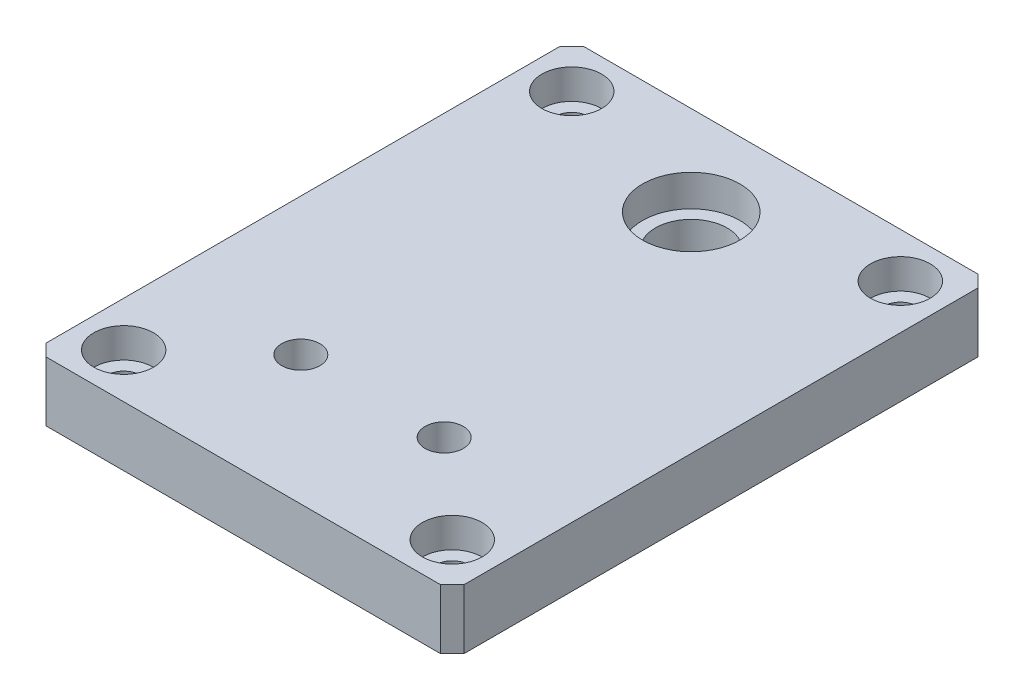
SolidWorks part; units mm, degrees
ref_plane "Front Plane" through (0, 0, 0) normal (0, 0, 1) x (1, 0, 0)
ref_plane "Top Plane" through (0, 0, 0) normal (0, 1, 0) x (1, 0, 0)
ref_plane "Right Plane" through (0, 0, 0) normal (1, 0, 0) x (0, 0, -1)
sketch "Sketch1" plane through (0, 0, 0) normal (0, 1, 0) x (1, 0, 0)
  line L1 (-35, -45) -> (35, -45)
  line L2 (-35, -45) -> (-35, 45)
  line L3 (-35, 45) -> (35, 45)
  line L4 (35, -45) -> (35, 45)
  line L5 (-35, -45) -> (35, 45) construction
  line L6 (-35, 45) -> (35, -45) construction
  point P0 (0, 0)
  dimension "D1" = 70
  dimension "D2" = 90
extrude "Boss-Extrude1" add sketch "Sketch1" along normal blind 10
sketch "Sketch4" plane through (0, 10, 0) normal (0, 1, 0) x (1, 0, 0)
  line L0 (-35, 45) -> (-35, -45) construction
  line L1 (35, 45) -> (-35, 45) construction
  line L3 (35, -45) -> (35, 45) construction
  line L4 (-35, -45) -> (35, -45) construction
  point P0 (-27.5, -37.5)
  point P2 (-27.5, 37.5)
  point P4 (27.5, 37.5)
  point P6 (27.5, -37.5)
  dimension "D1" = 7.5
  dimension "D2" = 7.5
  dimension "D3" = 7.5
  dimension "D4" = 7.5
hole_wizard "CBORE for M5 SHCS1" positions "Sketch4" profile "Sketch3" counterbore size "M5" standard "ANSI Metric" end condition through all
sketch "Sketch3" plane through (-27.5, 10, 37.5) normal (1, 0, 0) x (0, 0, 1)
  line L0 (0, 0) -> (0, 10)
  line L1 (0, 10) -> (2.75, 10)
  line L3 (2.75, 10) -> (2.75, 5)
  line L4 (2.75, 5) -> (5, 5)
  line L5 (5, 5) -> (5, 0)
  line L7 (5, 0) -> (0, 0)
  line L11 (0, -6.35) -> (0, 107.95) construction
  dimension "Thru Hole Dia." = 5.5
  dimension "Thru Hole Depth" = 10
  dimension "C'Bore Dia." = 10
  dimension "C'Bore Depth" = 5
sketch "Sketch7" plane through (0, 10, 0) normal (0, 1, 0) x (1, 0, 0)
  line L0 (35, 45) -> (-35, 45) construction
  point P0 (0, 30)
  dimension "D1" = 15
hole_wizard "Ø1.0mm Dowel Hole1" positions "Sketch7" profile "Sketch6" hole size "Ø1.0" standard "ANSI Metric"
sketch "Sketch6" plane through (0, 10, -30) normal (1, 0, 0) x (0, 0, 1)
  line L0 (0, 0) -> (0, 5.3)
  line L1 (0, 5.3) -> (8.15, 5.3)
  line L2 (8.15, 5.3) -> (8.15, 0)
  line L5 (8.15, 0) -> (0, 0)
  line L10 (0, 5.3) -> (-8.15, 5.3) construction
  line L11 (0, -6.35) -> (0, 107.95) construction
  dimension "Hole Dia." = 16.3
  dimension "Hole Depth" = 5.3
  dimension "Drill Angle" = 180
sketch "Sketch13" plane through (0, 4.7, 0) normal (0, 1, 0) x (1, 0, 0)
  point P0 (0, 30)
hole_wizard "Ø1.0mm Dowel Hole3" positions "Sketch13" profile "Sketch12" hole size "Ø1.0" standard "ANSI Metric" end condition through all
sketch "Sketch12" plane through (0, 4.7, -30) normal (1, 0, 0) x (0, 0, 1)
  line L0 (0, 0) -> (0, 4.7)
  line L1 (0, 4.7) -> (6, 4.7)
  line L2 (6, 4.7) -> (6, 0)
  line L5 (6, 0) -> (0, 0)
  line L11 (0, -6.35) -> (0, 107.95) construction
  dimension "Thru Hole Dia." = 12
  dimension "Thru Hole Depth" = 4.7
sketch "Sketch14" plane through (0, 10, 0) normal (0, 1, 0) x (1, 0, 0)
  circle A2 centre (12, -23.35) radius 3.2
  circle A3 centre (-12, -23.35) radius 3.2
  dimension "D5" = 6.4
  dimension "D6" = 6.4
  dimension "D1" = 23.35
  dimension "D2" = 12
  dimension "D3" = 12
  dimension "D4" = 23.35
extrude "Cut-Extrude1" cut sketch "Sketch14" against normal through all
chamfer "Chamfer1" distance 2 angle 45 4 edges at (35, 5, 45) (35, 5, -45) (-35, 5, -45) (-35, 5, 45)
equation "\"D1@Sketch4\" = 5 * 1.5"
equation "\"D2@Sketch4\" = \"D1@Sketch4\""
